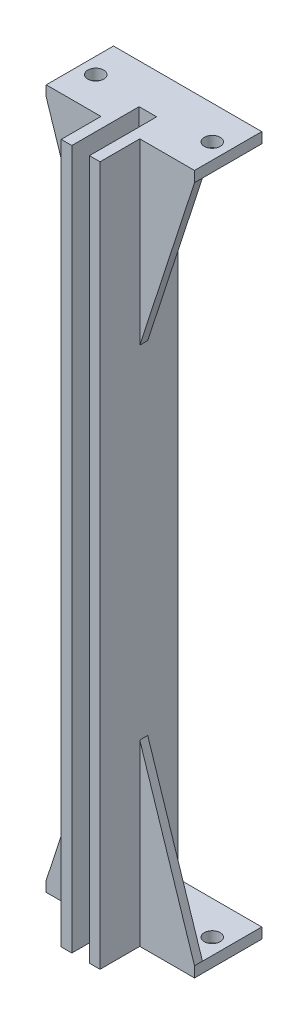
SolidWorks part; units mm, degrees
ref_plane "Front Plane" through (0, 0, 0) normal (0, 0, 1) x (1, 0, 0)
ref_plane "Top Plane" through (0, 0, 0) normal (0, 1, 0) x (1, 0, 0)
ref_plane "Right Plane" through (0, 0, 0) normal (1, 0, 0) x (0, 0, -1)
sketch "Sketch1" plane through (0, 0, 0) normal (0, 1, 0) x (1, 0, 0)
  line L0 (-3.6637, 0) -> (3.6637, 0)
  line L1 (3.6637, 0) -> (3.6637, -14.7)
  line L2 (3.6637, -14.7) -> (1.6637, -14.7)
  line L3 (1.6637, -14.7) -> (1.6637, -2)
  line L4 (1.6637, -2) -> (-1.6637, -2)
  line L5 (-1.6637, -2) -> (-1.6637, -14.7)
  line L6 (-1.6637, -14.7) -> (-3.6637, -14.7)
  line L7 (-3.6637, -14.7) -> (-3.6637, 0)
  line L8 (-11, -0.846) -> (11, -0.846) construction
  line L10 (-3.6637, 0) -> (-3.6637, -14.7)
  line L12 (-14, 5.504) -> (-14, -7.196)
  line L14 (3.6637, 0) -> (3.6637, -7.196)
  line L15 (3.6637, -7.196) -> (14, -7.196)
  line L16 (14, 5.504) -> (14, -7.196)
  line L17 (-14, -7.196) -> (-3.6637, -7.196)
  line L18 (-14, 5.504) -> (-3.6637, 5.504)
  line L19 (-3.6637, 5.504) -> (-3.6637, 0)
  line L20 (3.6637, 5.504) -> (14, 5.504)
  line L21 (3.6637, 5.504) -> (3.6637, 0)
  line L22 (-3.6637, 5.504) -> (3.6637, 5.504)
  circle A0 centre (-11, -0.846) radius 1.5
  circle A1 centre (11, -0.846) radius 1.5
  point P7 (0, 0)
  point P22 (0, -0.846)
  point P23 (0, -2)
  dimension "D5" = 3
  dimension "D1" = 3.3274
  dimension "D2" = 12.7
  dimension "D3" = 2
  dimension "D4" = 2
  dimension "D8" = 3
  dimension "D6" = 22
  dimension "D7" = 6.35
  dimension "D9" = 1.154
  dimension "D10" = 6.35
extrude "Boss-Extrude1" add sketch "Sketch1" along normal blind 2 contours A0 L10 L12 L7 | L10 L8 L4 L1 L0 | L8 L3 L2 L1 L14 | L16 L1 A1 L14 L15 | L22 L19 L0 L21 region at (0, 0, -2.752) region at (0, 0, 0.423) region at (-3.8274, 0, 0.423) region at (3.8274, 0, -2.752) region at (0, 0, 1.0027)
extrude "Boss-Extrude2" add sketch "Sketch1<3>" along normal blind 38.1 contours L8 L7 L6 L5 | L10 L8 L4 L1 L0 region at (0, 0, 0.423) region at (0, 0, 1.0027)
sketch "Sketch1<3>" plane through (0, 0, 0) normal (0, 1, 0) x (1, 0, 0) same geometry as "Sketch1"
sketch "Sketch2" plane through (0, 0, 7.196) normal (0, 0, -1) x (-1, 0, 0)
  line L0 (3.6637, 2) -> (3.6637, 33.75)
  line L2 (3.6637, 33.75) -> (14, 2)
  line L3 (14, 2) -> (3.6637, 2)
  line L4 (-14, 2) -> (-3.6637, 2)
  line L5 (-3.6637, 2) -> (-3.6637, 33.75)
  line L6 (-3.6637, 38.1) -> (-3.6637, 0) construction
  line L7 (-3.6637, 33.75) -> (-14, 2)
  line L9 (3.6637, 38.1) -> (3.6637, 0) construction
  dimension "D1" = 31.75
extrude "Boss-Extrude3" add sketch "Sketch2" along normal blind 1.5
sketch "Sketch6" plane through (0, 38.1, 0) normal (0, 1, 0) x (1, 0, 0)
  line L0 (1.6637, -14.7) -> (3.6637, -14.7)
  line L1 (-3.6637, 0) -> (3.6637, 0)
  line L2 (-3.6637, 0) -> (-3.6637, -14.7)
  line L3 (-3.6637, -14.7) -> (-1.6637, -14.7)
  line L4 (3.6637, 0) -> (3.6637, -14.7)
  line L5 (-1.6637, -2) -> (1.6637, -2)
  line L6 (-1.6637, -2) -> (-1.6637, -14.7)
  line L8 (1.6637, -2) -> (1.6637, -14.7)
extrude "Boss-Extrude6" add sketch "Sketch6" along normal blind 27.94
ref_plane "Plane1" through (0, 66.04, 0) normal (0, -1, 0) x (-1, 0, 0)
mirror "Mirror6" about plane through (0, 66.04, 0) normal (0, -1, 0) of bodies 107
equation "\"bottomThickness\"= .220in"
equation "\"wallThickness\"= .125in"
equation "\"D1@Sketch1\"=\"wallThickness\"+.006in"
